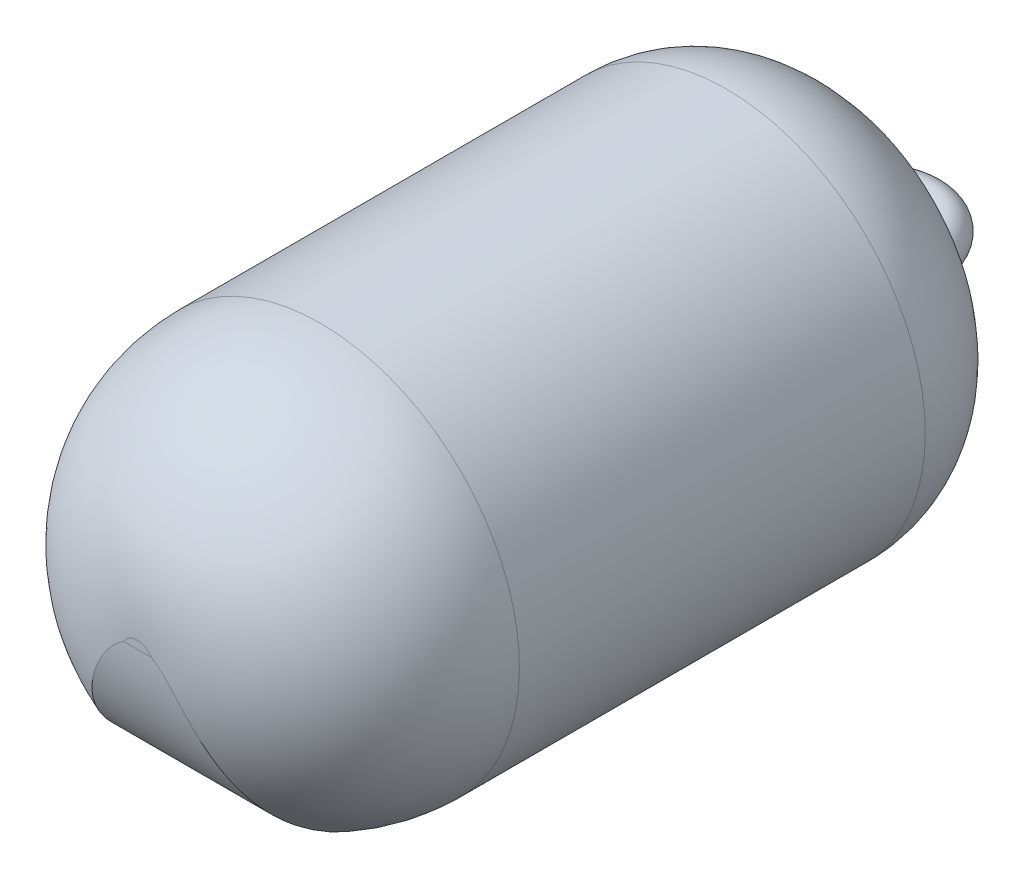
SolidWorks part; units mm, degrees
ref_plane "Alzado" through (0, 0, 0) normal (0, 0, 1) x (1, 0, 0)
ref_plane "Planta" through (0, 0, 0) normal (0, 1, 0) x (1, 0, 0)
ref_plane "Vista lateral" through (0, 0, 0) normal (1, 0, 0) x (0, 0, -1)
sketch "Croquis1" plane through (0, 0, 0) normal (0, 0, 1) x (1, 0, 0)
  circle A0 centre (0, 0) radius 25
  dimension "D1" = 50
extrude "Saliente-Extruir1" add sketch "Croquis1" along normal blind 90
sketch "Croquis3" plane through (0, 0, 0) normal (0, 1, 0) x (1, 0, 0)
  line L0 (0, 0) -> (0, 3) construction
  line L1 (-3, 0) -> (-3, 3)
  line L2 (25, 0) -> (-25, 0) construction
  line L3 (3, 0) -> (3, 3)
  arc A0 (-3, 3) -> (3, 3) centre (0, 3) cw
  dimension "D1" = 3
  dimension "D2" = 6
  dimension "D3" = 3
sketch "Croquis4" plane through (0, 0, 0) normal (0, 0, -1) x (-1, 0, 0)
  line L0 (3, 0) -> (-3, 0) construction
  circle A0 centre (-6, 0) radius 2.5
  dimension "D1" = 5
  dimension "D2" = 6
sweep "Barrer3" add profiles "Croquis4" path "Croquis3"
sketch "Croquis5" plane through (0, 0, 0) normal (0, 1, 0) x (1, 0, 0)
  line L0 (0, 0) -> (0, 6.5) construction
  line L1 (0, 0) -> (0, 3.25) construction
  arc A0 (3.5, 3) -> (-3.5, 3) centre (0, 3) ccw construction
fillet "Redondeo2" radius 16 1 edges at (25, 0, 0)
sketch "Croquis12" plane through (0, 0, 0) normal (0, 1, 0) x (1, 0, 0)
  line L0 (9, 0) -> (-9, 0) construction
  line L1 (25, -90) -> (-65, -90)
  line L2 (25, -90) -> (25, 0)
  line L3 (25, 0) -> (-65, 0)
  line L4 (-65, -90) -> (-65, 0)
extrude "Cortar-Extruir2" cut sketch "Croquis12" against normal blind 30 from offset 22 offset against normal yes
fillet "Redondeo3" radius 23 2 edges at (0, 25, 90) (0, -22, 90)
